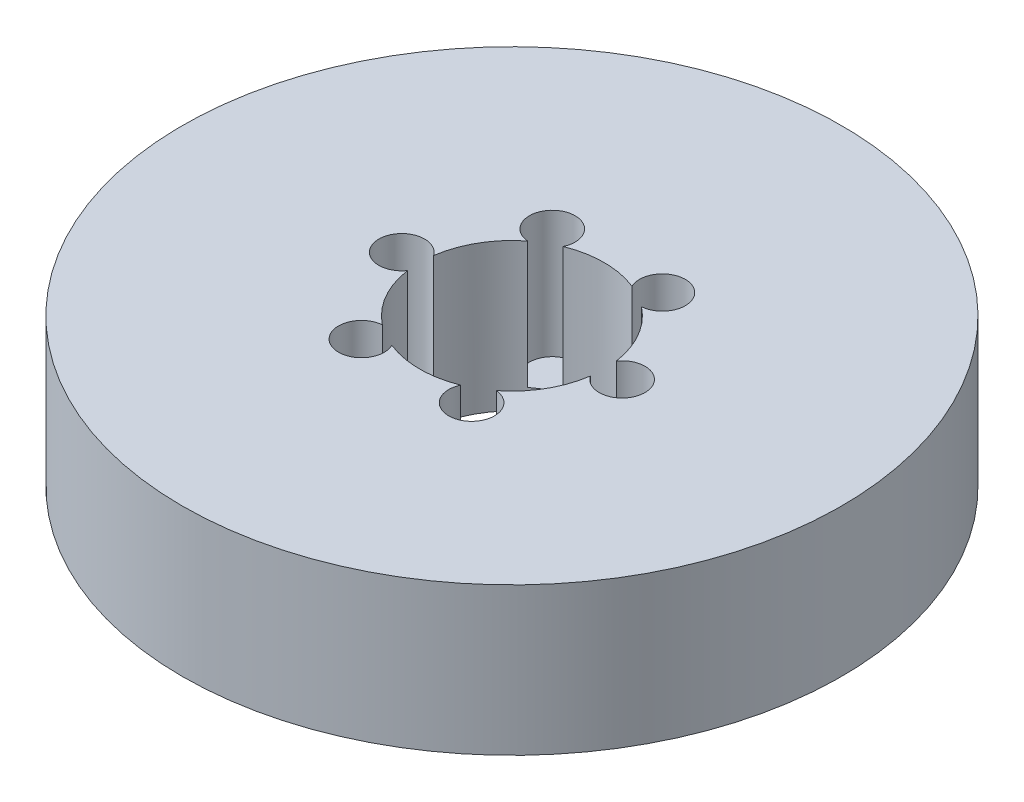
SolidWorks part; units mm, degrees
ref_plane "Front Plane" through (0, 0, 0) normal (0, 0, 1) x (1, 0, 0)
ref_plane "Top Plane" through (0, 0, 0) normal (0, 1, 0) x (1, 0, 0)
ref_plane "Right Plane" through (0, 0, 0) normal (1, 0, 0) x (0, 0, -1)
sketch "Sketch1" plane through (0, 0, 0) normal (0, 1, 0) x (1, 0, 0)
  circle A0 centre (0, 0) radius 62.5
  dimension "FLANGE_OD" = 125
extrude "Boss-Extrude1" add sketch "Sketch1" along normal blind 28
sketch "Sketch2" plane through (0, 0, 0) normal (0, 1, 0) x (1, 0, 0)
  circle A0 centre (0, 0) radius 17.5
  dimension "BORE_D" = 35
extrude "Cut-Extrude1" cut sketch "Sketch2" along normal through all
sketch "Sketch3" plane through (0, 28, 0) normal (0, 1, 0) x (1, 0, 0)
  circle A0 centre (0, 0) radius 20.8927 construction
  circle A1 centre (-20.8927, 0) radius 4.338
  dimension "BOLT_D" = 8.676
  dimension "BOLT_PCD" = 41.7854
extrude "Cut-Extrude2" cut sketch "Sketch3" against normal blind 24.0503
pattern_circular "CirPattern1" count 6 over 360 about axis through (0, 0, 0) along (0, 1, 0) of "Cut-Extrude2"
